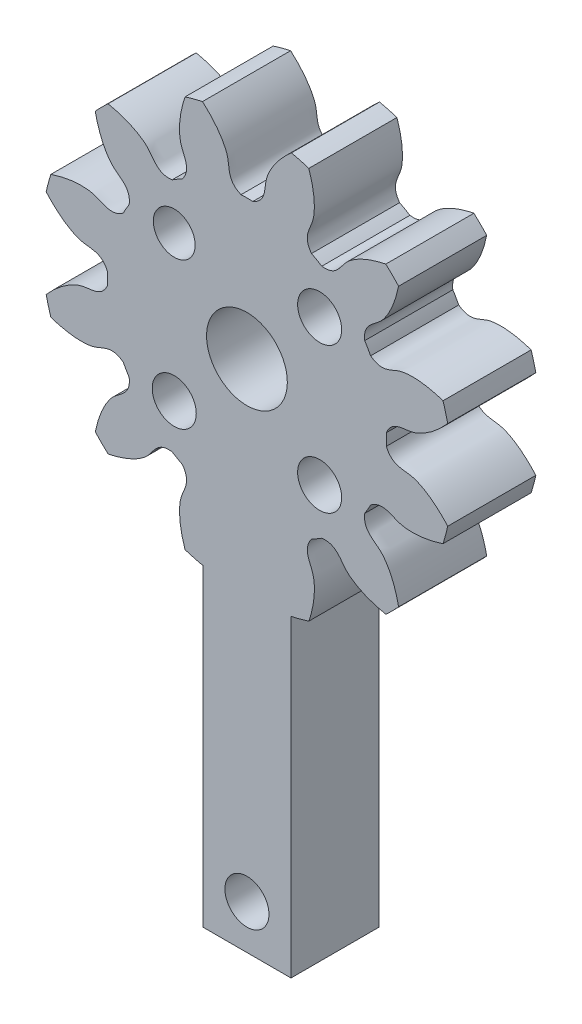
SolidWorks part; units mm, degrees
ref_plane "前视基准面" through (0, 0, 0) normal (0, 0, 1) x (1, 0, 0)
ref_plane "上视基准面" through (0, 0, 0) normal (0, 1, 0) x (1, 0, 0)
ref_plane "右视基准面" through (0, 0, 0) normal (1, 0, 0) x (0, 0, -1)
sketch "草图1" plane through (0, 0, 0) normal (0, 0, 1) x (1, 0, 0)
  circle A0 centre (0, 0) radius 14
extrude "凸台-拉伸1" add sketch "草图1" along normal blind 30
ref_axis "基准轴1" through (0, 0, -1.5) along (0, 0, 1)
sketch "草图2" plane through (0, 0, 0) normal (0, 0, 1) x (1, 0, 0)
  line L0 (0, 0) -> (0, 14) construction
  circle A0 centre (0, 0) radius 14 construction
  arc A1 (0.4017, 9.4915) -> (-0.4017, 9.4915) centre (0, 0) ccw
  arc A2 (6.9952, 15.7899) -> (-6.9952, 15.7899) centre (0, 0) ccw
  spline S0 degree 3 poles (0.4017, 9.4915) (1.3616, 9.8986) (1.1487, 10.6896) (1.3523, 11.379) (1.3652, 11.4198) (1.3805, 11.4647) (1.3981, 11.5135) (1.4183, 11.5661) (1.4413, 11.6225) (1.4671, 11.6826) (1.4961, 11.7462) (1.5282, 11.8133) (1.5637, 11.8838) (1.6028, 11.9576) (1.6455, 12.0345) (1.6919, 12.1144) (1.7423, 12.1973) (1.7968, 12.2829) (1.8555, 12.3712) (1.9185, 12.462) (1.9859, 12.5552) (2.0579, 12.6506) (2.1346, 12.7481) (2.2161, 12.8475) (2.3025, 12.9487) (2.3939, 13.0516) (2.4904, 13.1559) (2.5921, 13.2615) (2.6991, 13.3682) (2.8114, 13.4759) (2.9292, 13.5844) (3.0525, 13.6935) (3.1814, 13.803) (3.316, 13.9128) (3.4563, 14.0226) (3.6023, 14.1323) (3.7542, 14.2418) (3.912, 14.3507) (4.0756, 14.4589) (4.2452, 14.5663) (4.4208, 14.6726) (4.6024, 14.7776) (4.79, 14.8811) (4.9836, 14.983) (5.1832, 15.083) (5.3889, 15.1809) (5.6006, 15.2765) (5.8183, 15.3697) (6.042, 15.4602) (6.2717, 15.5478) (6.5888, 15.6615) (6.8312, 15.7402) (6.9952, 15.7899) knots 0 0 0 0 0.218015 0.222044 0.226546 0.231522 0.236972 0.242897 0.249295 0.256167 0.263513 0.271332 0.279626 0.288394 0.297636 0.307351 0.317541 0.328204 0.339341 0.350953 0.363038 0.375597 0.38863 0.402137 0.416118 0.430573 0.445502 0.460904 0.476781 0.493132 0.509956 0.527255 0.545027 0.563273 0.581994 0.601188 0.620856 0.640998 0.661614 0.682704 0.704268 0.726305 0.748817 0.771803 0.795262 0.819196 0.843603 0.868484 0.89384 0.919669 0.945972 1 1 1 1
  spline S1 degree 3 poles (-0.4017, 9.4915) (-1.3616, 9.8986) (-1.1487, 10.6896) (-1.3523, 11.379) (-1.3652, 11.4198) (-1.3805, 11.4647) (-1.3981, 11.5135) (-1.4183, 11.5661) (-1.4413, 11.6225) (-1.4671, 11.6826) (-1.4961, 11.7462) (-1.5282, 11.8133) (-1.5637, 11.8838) (-1.6028, 11.9576) (-1.6455, 12.0345) (-1.6919, 12.1144) (-1.7423, 12.1973) (-1.7968, 12.2829) (-1.8555, 12.3712) (-1.9185, 12.462) (-1.9859, 12.5552) (-2.0579, 12.6506) (-2.1346, 12.7481) (-2.2161, 12.8475) (-2.3025, 12.9487) (-2.3939, 13.0516) (-2.4904, 13.1559) (-2.5921, 13.2615) (-2.6991, 13.3682) (-2.8114, 13.4759) (-2.9292, 13.5844) (-3.0525, 13.6935) (-3.1814, 13.803) (-3.316, 13.9128) (-3.4563, 14.0226) (-3.6023, 14.1323) (-3.7542, 14.2418) (-3.912, 14.3507) (-4.0756, 14.4589) (-4.2452, 14.5663) (-4.4208, 14.6726) (-4.6024, 14.7776) (-4.79, 14.8811) (-4.9836, 14.983) (-5.1832, 15.083) (-5.3889, 15.1809) (-5.6006, 15.2765) (-5.8183, 15.3697) (-6.042, 15.4602) (-6.2717, 15.5478) (-6.5888, 15.6615) (-6.8312, 15.7402) (-6.9952, 15.7899) knots 0 0 0 0 0.218015 0.222044 0.226546 0.231522 0.236972 0.242897 0.249295 0.256167 0.263513 0.271332 0.279626 0.288394 0.297636 0.307351 0.317541 0.328204 0.339341 0.350953 0.363038 0.375597 0.38863 0.402137 0.416118 0.430573 0.445502 0.460904 0.476781 0.493132 0.509956 0.527255 0.545027 0.563273 0.581994 0.601188 0.620856 0.640998 0.661614 0.682704 0.704268 0.726305 0.748817 0.771803 0.795262 0.819196 0.843603 0.868484 0.89384 0.919669 0.945972 1 1 1 1
extrude "切除-拉伸1" cut sketch "草图2" along normal through all
pattern_circular "阵列(圆周)1" count 12 every 30 about axis through (0, 0, -1.5) along (0, 0, 1) of "切除-拉伸1"
sketch "草图3" plane through (0, 0, 0) normal (0, 0, 1) x (1, 0, 0)
  circle A0 centre (0, 0) radius 12 construction
  dimension "Dn" = 24
sketch "草图4" plane through (0, 0, 30) normal (0, 0, 1) x (1, 0, 0)
  line L0 (-4.75, 8.2272) -> (4.75, 8.2272) construction
  line L1 (4.95, -4.95) -> (-4.95, -4.95) construction
  line L2 (4.95, -4.95) -> (4.95, 4.95) construction
  line L3 (4.95, 4.95) -> (-4.95, 4.95) construction
  line L4 (-4.95, -4.95) -> (-4.95, 4.95) construction
  line L5 (4.95, -4.95) -> (-4.95, 4.95) construction
  line L6 (4.95, 4.95) -> (-4.95, -4.95) construction
  circle A0 centre (4.95, 4.95) radius 1.5
  circle A1 centre (4.95, -4.95) radius 1.5
  circle A2 centre (-4.95, -4.95) radius 1.5
  circle A3 centre (-4.95, 4.95) radius 1.4237
  arc A4 (-4.3979, 8.4207) -> (-5.0936, 8.019) centre (0, 0) ccw construction
  arc A5 (5.0936, 8.019) -> (4.3979, 8.4207) centre (0, 0) ccw construction
  point P0 (0, 0)
  dimension "D3" = 3
  dimension "D1" = 9.9
  dimension "D2" = 9.9
extrude "切除-拉伸2" cut sketch "草图4" against normal blind 10
sketch "草图5" plane through (0, 0, 0) normal (0, 0, -1) x (-1, 0, 0)
  arc A24 (5.0936, 8.019) -> (4.3979, 8.4207) centre (0, 0) ccw
  arc A25 (4.2145, 13.3506) -> (3.0255, 13.6692) centre (0, 0) ccw
  arc A26 (0.4017, 9.4915) -> (-0.4017, 9.4915) centre (0, 0) ccw
  arc A27 (-3.0255, 13.6692) -> (-4.2145, 13.3506) centre (0, 0) ccw
  arc A28 (-4.3979, 8.4207) -> (-5.0936, 8.019) centre (0, 0) ccw
  arc A29 (-9.4547, 10.3251) -> (-10.3251, 9.4547) centre (0, 0) ccw
  arc A30 (-8.019, 5.0936) -> (-8.4207, 4.3979) centre (0, 0) ccw
  arc A31 (-13.3506, 4.2145) -> (-13.6692, 3.0255) centre (0, 0) ccw
  arc A32 (-9.4915, 0.4017) -> (-9.4915, -0.4017) centre (0, 0) ccw
  arc A33 (-13.6692, -3.0255) -> (-13.3506, -4.2145) centre (0, 0) ccw
  arc A34 (-8.4207, -4.3979) -> (-8.019, -5.0936) centre (0, 0) ccw
  arc A35 (-10.3251, -9.4547) -> (-9.4547, -10.3251) centre (0, 0) ccw
  arc A36 (-5.0936, -8.019) -> (-4.3979, -8.4207) centre (0, 0) ccw
  arc A37 (-4.2145, -13.3506) -> (-3.0255, -13.6692) centre (0, 0) ccw
  arc A38 (-0.4017, -9.4915) -> (0.4017, -9.4915) centre (0, 0) ccw
  arc A39 (3.0255, -13.6692) -> (4.2145, -13.3506) centre (0, 0) ccw
  arc A40 (4.3979, -8.4207) -> (5.0936, -8.019) centre (0, 0) ccw
  arc A41 (9.4547, -10.3251) -> (10.3251, -9.4547) centre (0, 0) ccw
  arc A42 (8.019, -5.0936) -> (8.4207, -4.3979) centre (0, 0) ccw
  arc A43 (13.3506, -4.2145) -> (13.6692, -3.0255) centre (0, 0) ccw
  arc A44 (9.4915, -0.4017) -> (9.4915, 0.4017) centre (0, 0) ccw
  arc A45 (13.6692, 3.0255) -> (13.3506, 4.2145) centre (0, 0) ccw
  arc A46 (8.4207, 4.3979) -> (8.019, 5.0936) centre (0, 0) ccw
  arc A47 (10.3251, 9.4547) -> (9.4547, 10.3251) centre (0, 0) ccw
  arc A48 (5.0936, 8.019) -> (4.3979, 8.4207) centre (0, 0) ccw
  arc A49 (4.2145, 13.3506) -> (3.0255, 13.6692) centre (0, 0) ccw
  arc A50 (0.4017, 9.4915) -> (-0.4017, 9.4915) centre (0, 0) ccw
  arc A51 (-3.0255, 13.6692) -> (-4.2145, 13.3506) centre (0, 0) ccw
  arc A52 (-4.3979, 8.4207) -> (-5.0936, 8.019) centre (0, 0) ccw
  arc A53 (-9.4547, 10.3251) -> (-10.3251, 9.4547) centre (0, 0) ccw
  arc A54 (-8.019, 5.0936) -> (-8.4207, 4.3979) centre (0, 0) ccw
  arc A55 (-13.3506, 4.2145) -> (-13.6692, 3.0255) centre (0, 0) ccw
  arc A56 (-9.4915, 0.4017) -> (-9.4915, -0.4017) centre (0, 0) ccw
  arc A57 (-13.6692, -3.0255) -> (-13.3506, -4.2145) centre (0, 0) ccw
  arc A58 (-8.4207, -4.3979) -> (-8.019, -5.0936) centre (0, 0) ccw
  arc A59 (-10.3251, -9.4547) -> (-9.4547, -10.3251) centre (0, 0) ccw
  arc A60 (-5.0936, -8.019) -> (-4.3979, -8.4207) centre (0, 0) ccw
  arc A61 (-4.2145, -13.3506) -> (-3.0255, -13.6692) centre (0, 0) ccw
  arc A62 (-0.4017, -9.4915) -> (0.4017, -9.4915) centre (0, 0) ccw
  arc A63 (3.0255, -13.6692) -> (4.2145, -13.3506) centre (0, 0) ccw
  arc A64 (4.3979, -8.4207) -> (5.0936, -8.019) centre (0, 0) ccw
  arc A65 (9.4547, -10.3251) -> (10.3251, -9.4547) centre (0, 0) ccw
  arc A66 (8.019, -5.0936) -> (8.4207, -4.3979) centre (0, 0) ccw
  arc A67 (13.3506, -4.2145) -> (13.6692, -3.0255) centre (0, 0) ccw
  arc A68 (9.4915, -0.4017) -> (9.4915, 0.4017) centre (0, 0) ccw
  arc A69 (13.6692, 3.0255) -> (13.3506, 4.2145) centre (0, 0) ccw
  arc A70 (8.4207, 4.3979) -> (8.019, 5.0936) centre (0, 0) ccw
  arc A71 (10.3251, 9.4547) -> (9.4547, 10.3251) centre (0, 0) ccw
  spline S24 degree 3 poles (-2368.8794, 1837.9661) (113.0421, -150.6443) (38.3111, 18.3423) (8.7386, 10.1508) (8.4722, 10.0654) (8.2264, 9.9757) (8.0011, 9.883) (7.7961, 9.789) (7.6111, 9.695) (7.4457, 9.6025) (7.2995, 9.5129) (7.172, 9.4276) (7.0778, 9.359) (6.9977, 9.2968) (6.9309, 9.2418) (6.8721, 9.1892) (0.5786, 3.2069) (39.4786, -48.9386) (-2052.1534, 2191.1398) knots -9.086932 -9.086932 -9.086932 -9.086932 0.523219 0.554498 0.583882 0.61137 0.636962 0.660659 0.682459 0.702364 0.720374 0.736487 0.750705 0.757103 0.768478 0.777956 0.781985 3.505334 3.505334 3.505334 3.505334 only from (9.4547, 10.3251) to (5.0936, 8.019)
  spline S25 degree 3 poles (2923.6721, -681.6501) (-62.1215, 9.7202) (2.4879, 2.1045) (4.522, 10.546) (4.5381, 10.6233) (4.556, 10.7301) (4.5718, 10.8554) (4.5842, 10.9992) (4.5917, 11.1614) (4.5929, 11.3419) (4.5862, 11.5403) (4.5702, 11.7563) (4.5437, 11.9893) (4.505, 12.239) (4.453, 12.5046) (4.3862, 12.7855) (-4.0276, 42.7945) (-187.8553, 19.7333) (2778.1998, -1127.4538) knots -2.505338 -2.505338 -2.505338 -2.505338 0.218015 0.222044 0.231522 0.242897 0.256167 0.271332 0.288394 0.307351 0.328204 0.350953 0.375597 0.402137 0.430573 0.460904 0.493132 10.252695 10.252695 10.252695 10.252695 only from (4.3979, 8.4207) to (4.2145, 13.3506)
  spline S26 degree 3 poles (-2970.4928, 407.2856) (173.2195, -73.9407) (24.0073, 35.0405) (2.4924, 13.1601) (2.3045, 12.953) (2.1365, 12.7524) (1.9877, 12.5595) (1.8571, 12.3755) (1.7439, 12.2016) (1.6469, 12.0389) (1.5651, 11.8882) (1.4973, 11.7506) (1.4501, 11.6441) (1.4118, 11.5501) (1.3815, 11.4691) (1.3568, 11.3941) (-1.1024, 3.0665) (58.6587, -22.6428) (-2872.7869, 871.506) knots -9.086932 -9.086932 -9.086932 -9.086932 0.523219 0.554498 0.583882 0.61137 0.636962 0.660659 0.682459 0.702364 0.720374 0.736487 0.750705 0.757103 0.768478 0.777956 0.781985 3.505334 3.505334 3.505334 3.505334 only from (3.0255, 13.6692) to (0.4017, 9.4915)
  spline S27 degree 3 poles (2872.7993, 871.5098) (-58.6589, -22.6429) (1.1024, 3.0665) (-1.3568, 11.3941) (-1.3815, 11.4691) (-1.4194, 11.5705) (-1.4684, 11.687) (-1.5295, 11.8177) (-1.6042, 11.962) (-1.6934, 12.1188) (-1.7984, 12.2873) (-1.9202, 12.4663) (-2.0597, 12.6549) (-2.218, 12.8518) (-2.3959, 13.0558) (-2.5942, 13.2657) (-24.8852, 35.0474) (-172.5541, -76.8381) (2969.7185, 412.6963) knots -2.505338 -2.505338 -2.505338 -2.505338 0.218015 0.222044 0.231522 0.242897 0.256167 0.271332 0.288394 0.307351 0.328204 0.350953 0.375597 0.402137 0.430573 0.460904 0.493132 10.252695 10.252695 10.252695 10.252695 only from (-0.4017, 9.4915) to (-3.0255, 13.6692)
  spline S28 degree 3 poles (-2776.1651, -1132.5267) (186.9828, 22.5752) (3.2707, 42.3496) (-4.4215, 12.6432) (-4.4808, 12.3699) (-4.5259, 12.1121) (-4.5584, 11.8707) (-4.5794, 11.6461) (-4.5906, 11.4389) (-4.5932, 11.2494) (-4.5887, 11.078) (-4.5786, 10.925) (-4.5662, 10.8091) (-4.5524, 10.7085) (-4.5381, 10.6233) (-4.522, 10.546) (-2.4879, 2.1045) (62.1214, 9.7201) (-2923.6594, -681.6471) knots -9.086932 -9.086932 -9.086932 -9.086932 0.523219 0.554498 0.583882 0.61137 0.636962 0.660659 0.682459 0.702364 0.720374 0.736487 0.750705 0.757103 0.768478 0.777956 0.781985 3.505334 3.505334 3.505334 3.505334 only from (-4.2145, 13.3506) to (-4.3979, 8.4207)
  spline S29 degree 3 poles (2052.1623, 2191.1493) (-39.4787, -48.9387) (-0.5786, 3.2069) (-6.8721, 9.1892) (-6.9309, 9.2418) (-7.0145, 9.3106) (-7.1151, 9.387) (-7.2335, 9.4697) (-7.3702, 9.5573) (-7.5259, 9.6485) (-7.7011, 9.7419) (-7.8961, 9.8361) (-8.1112, 9.9296) (-8.3468, 10.021) (-8.6028, 10.1087) (-8.8795, 10.1914) (-39.0749, 17.9093) (-111.0172, -152.8208) (2365.5035, 1842.2647) knots -2.505338 -2.505338 -2.505338 -2.505338 0.218015 0.222044 0.231522 0.242897 0.256167 0.271332 0.288394 0.307351 0.328204 0.350953 0.375597 0.402137 0.430573 0.460904 0.493132 10.252695 10.252695 10.252695 10.252695 only from (-5.0936, 8.019) to (-9.4547, 10.3251)
  spline S30 degree 3 poles (-1837.9661, -2368.8794) (150.6443, 113.0421) (-18.3423, 38.3111) (-10.1508, 8.7386) (-10.0654, 8.4722) (-9.9757, 8.2264) (-9.883, 8.0011) (-9.789, 7.7961) (-9.695, 7.6111) (-9.6025, 7.4457) (-9.5129, 7.2995) (-9.4276, 7.172) (-9.359, 7.0778) (-9.2968, 6.9977) (-9.2418, 6.9309) (-9.1892, 6.8721) (-3.2069, 0.5786) (48.9386, 39.4786) (-2191.1398, -2052.1534) knots -9.086932 -9.086932 -9.086932 -9.086932 0.523219 0.554498 0.583882 0.61137 0.636962 0.660659 0.682459 0.702364 0.720374 0.736487 0.750705 0.757103 0.768478 0.777956 0.781985 3.505334 3.505334 3.505334 3.505334 only from (-10.3251, 9.4547) to (-8.019, 5.0936)
  spline S31 degree 3 poles (681.6501, 2923.6721) (-9.7202, -62.1215) (-2.1045, 2.4879) (-10.546, 4.522) (-10.6233, 4.5381) (-10.7301, 4.556) (-10.8554, 4.5718) (-10.9992, 4.5842) (-11.1614, 4.5917) (-11.3419, 4.5929) (-11.5403, 4.5862) (-11.7563, 4.5702) (-11.9893, 4.5437) (-12.239, 4.505) (-12.5046, 4.453) (-12.7855, 4.3862) (-42.7945, -4.0276) (-19.7333, -187.8553) (1127.4538, 2778.1998) knots -2.505338 -2.505338 -2.505338 -2.505338 0.218015 0.222044 0.231522 0.242897 0.256167 0.271332 0.288394 0.307351 0.328204 0.350953 0.375597 0.402137 0.430573 0.460904 0.493132 10.252695 10.252695 10.252695 10.252695 only from (-8.4207, 4.3979) to (-13.3506, 4.2145)
  spline S32 degree 3 poles (-407.2856, -2970.4928) (73.9407, 173.2195) (-35.0405, 24.0073) (-13.1601, 2.4924) (-12.953, 2.3045) (-12.7524, 2.1365) (-12.5595, 1.9877) (-12.3755, 1.8571) (-12.2016, 1.7439) (-12.0389, 1.6469) (-11.8882, 1.5651) (-11.7506, 1.4973) (-11.6441, 1.4501) (-11.5501, 1.4118) (-11.4691, 1.3815) (-11.3941, 1.3568) (-3.0665, -1.1024) (22.6428, 58.6587) (-871.506, -2872.7869) knots -9.086932 -9.086932 -9.086932 -9.086932 0.523219 0.554498 0.583882 0.61137 0.636962 0.660659 0.682459 0.702364 0.720374 0.736487 0.750705 0.757103 0.768478 0.777956 0.781985 3.505334 3.505334 3.505334 3.505334 only from (-13.6692, 3.0255) to (-9.4915, 0.4017)
  spline S33 degree 3 poles (-871.5098, 2872.7993) (22.6429, -58.6589) (-3.0665, 1.1024) (-11.3941, -1.3568) (-11.4691, -1.3815) (-11.5705, -1.4194) (-11.687, -1.4684) (-11.8177, -1.5295) (-11.962, -1.6042) (-12.1188, -1.6934) (-12.2873, -1.7984) (-12.4663, -1.9202) (-12.6549, -2.0597) (-12.8518, -2.218) (-13.0558, -2.3959) (-13.2657, -2.5942) (-35.0474, -24.8852) (76.8381, -172.5541) (-412.6963, 2969.7185) knots -2.505338 -2.505338 -2.505338 -2.505338 0.218015 0.222044 0.231522 0.242897 0.256167 0.271332 0.288394 0.307351 0.328204 0.350953 0.375597 0.402137 0.430573 0.460904 0.493132 10.252695 10.252695 10.252695 10.252695 only from (-9.4915, -0.4017) to (-13.6692, -3.0255)
  spline S34 degree 3 poles (1132.5267, -2776.1651) (-22.5752, 186.9828) (-42.3496, 3.2707) (-12.6432, -4.4215) (-12.3699, -4.4808) (-12.1121, -4.5259) (-11.8707, -4.5584) (-11.6461, -4.5794) (-11.4389, -4.5906) (-11.2494, -4.5932) (-11.078, -4.5887) (-10.925, -4.5786) (-10.8091, -4.5662) (-10.7085, -4.5524) (-10.6233, -4.5381) (-10.546, -4.522) (-2.1045, -2.4879) (-9.7201, 62.1214) (681.6471, -2923.6594) knots -9.086932 -9.086932 -9.086932 -9.086932 0.523219 0.554498 0.583882 0.61137 0.636962 0.660659 0.682459 0.702364 0.720374 0.736487 0.750705 0.757103 0.768478 0.777956 0.781985 3.505334 3.505334 3.505334 3.505334 only from (-13.3506, -4.2145) to (-8.4207, -4.3979)
  spline S35 degree 3 poles (-2191.1493, 2052.1623) (48.9387, -39.4787) (-3.2069, -0.5786) (-9.1892, -6.8721) (-9.2418, -6.9309) (-9.3106, -7.0145) (-9.387, -7.1151) (-9.4697, -7.2335) (-9.5573, -7.3702) (-9.6485, -7.5259) (-9.7419, -7.7011) (-9.8361, -7.8961) (-9.9296, -8.1112) (-10.021, -8.3468) (-10.1087, -8.6028) (-10.1914, -8.8795) (-17.9093, -39.0749) (152.8208, -111.0172) (-1842.2647, 2365.5035) knots -2.505338 -2.505338 -2.505338 -2.505338 0.218015 0.222044 0.231522 0.242897 0.256167 0.271332 0.288394 0.307351 0.328204 0.350953 0.375597 0.402137 0.430573 0.460904 0.493132 10.252695 10.252695 10.252695 10.252695 only from (-8.019, -5.0936) to (-10.3251, -9.4547)
  spline S36 degree 3 poles (2368.8794, -1837.9661) (-113.0421, 150.6443) (-38.3111, -18.3423) (-8.7386, -10.1508) (-8.4722, -10.0654) (-8.2264, -9.9757) (-8.0011, -9.883) (-7.7961, -9.789) (-7.6111, -9.695) (-7.4457, -9.6025) (-7.2995, -9.5129) (-7.172, -9.4276) (-7.0778, -9.359) (-6.9977, -9.2968) (-6.9309, -9.2418) (-6.8721, -9.1892) (-0.5786, -3.2069) (-39.4786, 48.9386) (2052.1534, -2191.1398) knots -9.086932 -9.086932 -9.086932 -9.086932 0.523219 0.554498 0.583882 0.61137 0.636962 0.660659 0.682459 0.702364 0.720374 0.736487 0.750705 0.757103 0.768478 0.777956 0.781985 3.505334 3.505334 3.505334 3.505334 only from (-9.4547, -10.3251) to (-5.0936, -8.019)
  spline S37 degree 3 poles (-2923.6721, 681.6501) (62.1215, -9.7202) (-2.4879, -2.1045) (-4.522, -10.546) (-4.5381, -10.6233) (-4.556, -10.7301) (-4.5718, -10.8554) (-4.5842, -10.9992) (-4.5917, -11.1614) (-4.5929, -11.3419) (-4.5862, -11.5403) (-4.5702, -11.7563) (-4.5437, -11.9893) (-4.505, -12.239) (-4.453, -12.5046) (-4.3862, -12.7855) (4.0276, -42.7945) (187.8553, -19.7333) (-2778.1998, 1127.4538) knots -2.505338 -2.505338 -2.505338 -2.505338 0.218015 0.222044 0.231522 0.242897 0.256167 0.271332 0.288394 0.307351 0.328204 0.350953 0.375597 0.402137 0.430573 0.460904 0.493132 10.252695 10.252695 10.252695 10.252695 only from (-4.3979, -8.4207) to (-4.2145, -13.3506)
  spline S38 degree 3 poles (2970.4928, -407.2856) (-173.2195, 73.9407) (-24.0073, -35.0405) (-2.4924, -13.1601) (-2.3045, -12.953) (-2.1365, -12.7524) (-1.9877, -12.5595) (-1.8571, -12.3755) (-1.7439, -12.2016) (-1.6469, -12.0389) (-1.5651, -11.8882) (-1.4973, -11.7506) (-1.4501, -11.6441) (-1.4118, -11.5501) (-1.3815, -11.4691) (-1.3568, -11.3941) (1.1024, -3.0665) (-58.6587, 22.6428) (2872.7869, -871.506) knots -9.086932 -9.086932 -9.086932 -9.086932 0.523219 0.554498 0.583882 0.61137 0.636962 0.660659 0.682459 0.702364 0.720374 0.736487 0.750705 0.757103 0.768478 0.777956 0.781985 3.505334 3.505334 3.505334 3.505334 only from (-3.0255, -13.6692) to (-0.4017, -9.4915)
  spline S39 degree 3 poles (-2872.7993, -871.5098) (58.6589, 22.6429) (-1.1024, -3.0665) (1.3568, -11.3941) (1.3815, -11.4691) (1.4194, -11.5705) (1.4684, -11.687) (1.5295, -11.8177) (1.6042, -11.962) (1.6934, -12.1188) (1.7984, -12.2873) (1.9202, -12.4663) (2.0597, -12.6549) (2.218, -12.8518) (2.3959, -13.0558) (2.5942, -13.2657) (24.8852, -35.0474) (172.5541, 76.8381) (-2969.7185, -412.6963) knots -2.505338 -2.505338 -2.505338 -2.505338 0.218015 0.222044 0.231522 0.242897 0.256167 0.271332 0.288394 0.307351 0.328204 0.350953 0.375597 0.402137 0.430573 0.460904 0.493132 10.252695 10.252695 10.252695 10.252695 only from (0.4017, -9.4915) to (3.0255, -13.6692)
  spline S40 degree 3 poles (2776.1651, 1132.5267) (-186.9828, -22.5752) (-3.2707, -42.3496) (4.4215, -12.6432) (4.4808, -12.3699) (4.5259, -12.1121) (4.5584, -11.8707) (4.5794, -11.6461) (4.5906, -11.4389) (4.5932, -11.2494) (4.5887, -11.078) (4.5786, -10.925) (4.5662, -10.8091) (4.5524, -10.7085) (4.5381, -10.6233) (4.522, -10.546) (2.4879, -2.1045) (-62.1214, -9.7201) (2923.6594, 681.6471) knots -9.086932 -9.086932 -9.086932 -9.086932 0.523219 0.554498 0.583882 0.61137 0.636962 0.660659 0.682459 0.702364 0.720374 0.736487 0.750705 0.757103 0.768478 0.777956 0.781985 3.505334 3.505334 3.505334 3.505334 only from (4.2145, -13.3506) to (4.3979, -8.4207)
  spline S41 degree 3 poles (-2052.1623, -2191.1493) (39.4787, 48.9387) (0.5786, -3.2069) (6.8721, -9.1892) (6.9309, -9.2418) (7.0145, -9.3106) (7.1151, -9.387) (7.2335, -9.4697) (7.3702, -9.5573) (7.5259, -9.6485) (7.7011, -9.7419) (7.8961, -9.8361) (8.1112, -9.9296) (8.3468, -10.021) (8.6028, -10.1087) (8.8795, -10.1914) (39.0749, -17.9093) (111.0172, 152.8208) (-2365.5035, -1842.2647) knots -2.505338 -2.505338 -2.505338 -2.505338 0.218015 0.222044 0.231522 0.242897 0.256167 0.271332 0.288394 0.307351 0.328204 0.350953 0.375597 0.402137 0.430573 0.460904 0.493132 10.252695 10.252695 10.252695 10.252695 only from (5.0936, -8.019) to (9.4547, -10.3251)
  spline S42 degree 3 poles (1837.9661, 2368.8794) (-150.6443, -113.0421) (18.3423, -38.3111) (10.1508, -8.7386) (10.0654, -8.4722) (9.9757, -8.2264) (9.883, -8.0011) (9.789, -7.7961) (9.695, -7.6111) (9.6025, -7.4457) (9.5129, -7.2995) (9.4276, -7.172) (9.359, -7.0778) (9.2968, -6.9977) (9.2418, -6.9309) (9.1892, -6.8721) (3.2069, -0.5786) (-48.9386, -39.4786) (2191.1398, 2052.1534) knots -9.086932 -9.086932 -9.086932 -9.086932 0.523219 0.554498 0.583882 0.61137 0.636962 0.660659 0.682459 0.702364 0.720374 0.736487 0.750705 0.757103 0.768478 0.777956 0.781985 3.505334 3.505334 3.505334 3.505334 only from (10.3251, -9.4547) to (8.019, -5.0936)
  spline S43 degree 3 poles (-681.6501, -2923.6721) (9.7202, 62.1215) (2.1045, -2.4879) (10.546, -4.522) (10.6233, -4.5381) (10.7301, -4.556) (10.8554, -4.5718) (10.9992, -4.5842) (11.1614, -4.5917) (11.3419, -4.5929) (11.5403, -4.5862) (11.7563, -4.5702) (11.9893, -4.5437) (12.239, -4.505) (12.5046, -4.453) (12.7855, -4.3862) (42.7945, 4.0276) (19.7333, 187.8553) (-1127.4538, -2778.1998) knots -2.505338 -2.505338 -2.505338 -2.505338 0.218015 0.222044 0.231522 0.242897 0.256167 0.271332 0.288394 0.307351 0.328204 0.350953 0.375597 0.402137 0.430573 0.460904 0.493132 10.252695 10.252695 10.252695 10.252695 only from (8.4207, -4.3979) to (13.3506, -4.2145)
  spline S44 degree 3 poles (407.2856, 2970.4928) (-73.9407, -173.2195) (35.0405, -24.0073) (13.1601, -2.4924) (12.953, -2.3045) (12.7524, -2.1365) (12.5595, -1.9877) (12.3755, -1.8571) (12.2016, -1.7439) (12.0389, -1.6469) (11.8882, -1.5651) (11.7506, -1.4973) (11.6441, -1.4501) (11.5501, -1.4118) (11.4691, -1.3815) (11.3941, -1.3568) (3.0665, 1.1024) (-22.6428, -58.6587) (871.506, 2872.7869) knots -9.086932 -9.086932 -9.086932 -9.086932 0.523219 0.554498 0.583882 0.61137 0.636962 0.660659 0.682459 0.702364 0.720374 0.736487 0.750705 0.757103 0.768478 0.777956 0.781985 3.505334 3.505334 3.505334 3.505334 only from (13.6692, -3.0255) to (9.4915, -0.4017)
  spline S45 degree 3 poles (871.5098, -2872.7993) (-22.6429, 58.6589) (3.0665, -1.1024) (11.3941, 1.3568) (11.4691, 1.3815) (11.5705, 1.4194) (11.687, 1.4684) (11.8177, 1.5295) (11.962, 1.6042) (12.1188, 1.6934) (12.2873, 1.7984) (12.4663, 1.9202) (12.6549, 2.0597) (12.8518, 2.218) (13.0558, 2.3959) (13.2657, 2.5942) (35.0474, 24.8852) (-76.8381, 172.5541) (412.6963, -2969.7185) knots -2.505338 -2.505338 -2.505338 -2.505338 0.218015 0.222044 0.231522 0.242897 0.256167 0.271332 0.288394 0.307351 0.328204 0.350953 0.375597 0.402137 0.430573 0.460904 0.493132 10.252695 10.252695 10.252695 10.252695 only from (9.4915, 0.4017) to (13.6692, 3.0255)
  spline S46 degree 3 poles (-1132.5267, 2776.1651) (22.5752, -186.9828) (42.3496, -3.2707) (12.6432, 4.4215) (12.3699, 4.4808) (12.1121, 4.5259) (11.8707, 4.5584) (11.6461, 4.5794) (11.4389, 4.5906) (11.2494, 4.5932) (11.078, 4.5887) (10.925, 4.5786) (10.8091, 4.5662) (10.7085, 4.5524) (10.6233, 4.5381) (10.546, 4.522) (2.1045, 2.4879) (9.7201, -62.1214) (-681.6471, 2923.6594) knots -9.086932 -9.086932 -9.086932 -9.086932 0.523219 0.554498 0.583882 0.61137 0.636962 0.660659 0.682459 0.702364 0.720374 0.736487 0.750705 0.757103 0.768478 0.777956 0.781985 3.505334 3.505334 3.505334 3.505334 only from (13.3506, 4.2145) to (8.4207, 4.3979)
  spline S47 degree 3 poles (2191.1493, -2052.1623) (-48.9387, 39.4787) (3.2069, 0.5786) (9.1892, 6.8721) (9.2418, 6.9309) (9.3106, 7.0145) (9.387, 7.1151) (9.4697, 7.2335) (9.5573, 7.3702) (9.6485, 7.5259) (9.7419, 7.7011) (9.8361, 7.8961) (9.9296, 8.1112) (10.021, 8.3468) (10.1087, 8.6028) (10.1914, 8.8795) (17.9093, 39.0749) (-152.8208, 111.0172) (1842.2647, -2365.5035) knots -2.505338 -2.505338 -2.505338 -2.505338 0.218015 0.222044 0.231522 0.242897 0.256167 0.271332 0.288394 0.307351 0.328204 0.350953 0.375597 0.402137 0.430573 0.460904 0.493132 10.252695 10.252695 10.252695 10.252695 only from (8.019, 5.0936) to (10.3251, 9.4547)
  spline S48 degree 3 poles (9.4547, 10.3251) (9.309, 10.2963) (9.0672, 10.2418) (8.7386, 10.1508) (8.4722, 10.0654) (8.2264, 9.9757) (8.0011, 9.883) (7.7961, 9.789) (7.6111, 9.695) (7.4457, 9.6025) (7.2995, 9.5129) (7.172, 9.4276) (7.0778, 9.359) (6.9977, 9.2968) (6.9309, 9.2418) (6.8721, 9.1892) (6.3397, 8.6831) (6.1285, 7.8917) (5.0936, 8.019) knots 0.476404 0.476404 0.476404 0.476404 0.523219 0.554498 0.583882 0.61137 0.636962 0.660659 0.682459 0.702364 0.720374 0.736487 0.750705 0.757103 0.768478 0.777956 0.781985 1 1 1 1
  spline S49 degree 3 poles (4.3979, 8.4207) (3.7701, 9.2532) (4.35, 9.8319) (4.522, 10.546) (4.5381, 10.6233) (4.556, 10.7301) (4.5718, 10.8554) (4.5842, 10.9992) (4.5917, 11.1614) (4.5929, 11.3419) (4.5862, 11.5403) (4.5702, 11.7563) (4.5437, 11.9893) (4.505, 12.239) (4.453, 12.5046) (4.3862, 12.7855) (4.3065, 13.0698) (4.2457, 13.2591) (4.2145, 13.3506) knots 0 0 0 0 0.218015 0.222044 0.231522 0.242897 0.256167 0.271332 0.288394 0.307351 0.328204 0.350953 0.375597 0.402137 0.430573 0.460904 0.493132 0.523596 0.523596 0.523596 0.523596
  spline S50 degree 3 poles (3.0255, 13.6692) (2.9137, 13.5714) (2.7316, 13.4033) (2.4924, 13.1601) (2.3045, 12.953) (2.1365, 12.7524) (1.9877, 12.5595) (1.8571, 12.3755) (1.7439, 12.2016) (1.6469, 12.0389) (1.5651, 11.8882) (1.4973, 11.7506) (1.4501, 11.6441) (1.4118, 11.5501) (1.3815, 11.4691) (1.3568, 11.3941) (1.1487, 10.6896) (1.3616, 9.8986) (0.4017, 9.4915) knots 0.476404 0.476404 0.476404 0.476404 0.523219 0.554498 0.583882 0.61137 0.636962 0.660659 0.682459 0.702364 0.720374 0.736487 0.750705 0.757103 0.768478 0.777956 0.781985 1 1 1 1
  spline S51 degree 3 poles (-0.4017, 9.4915) (-1.3616, 9.8986) (-1.1487, 10.6896) (-1.3568, 11.3941) (-1.3815, 11.4691) (-1.4194, 11.5705) (-1.4684, 11.687) (-1.5295, 11.8177) (-1.6042, 11.962) (-1.6934, 12.1188) (-1.7984, 12.2873) (-1.9202, 12.4663) (-2.0597, 12.6549) (-2.218, 12.8518) (-2.3959, 13.0558) (-2.5942, 13.2657) (-2.8053, 13.472) (-2.9527, 13.6056) (-3.0255, 13.6692) knots 0 0 0 0 0.218015 0.222044 0.231522 0.242897 0.256167 0.271332 0.288394 0.307351 0.328204 0.350953 0.375597 0.402137 0.430573 0.460904 0.493132 0.523596 0.523596 0.523596 0.523596
  spline S52 degree 3 poles (-4.2145, 13.3506) (-4.2624, 13.21) (-4.3361, 12.9734) (-4.4215, 12.6432) (-4.4808, 12.3699) (-4.5259, 12.1121) (-4.5584, 11.8707) (-4.5794, 11.6461) (-4.5906, 11.4389) (-4.5932, 11.2494) (-4.5887, 11.078) (-4.5786, 10.925) (-4.5662, 10.8091) (-4.5524, 10.7085) (-4.5381, 10.6233) (-4.522, 10.546) (-4.35, 9.8319) (-3.7701, 9.2532) (-4.3979, 8.4207) knots 0.476404 0.476404 0.476404 0.476404 0.523219 0.554498 0.583882 0.61137 0.636962 0.660659 0.682459 0.702364 0.720374 0.736487 0.750705 0.757103 0.768478 0.777956 0.781985 1 1 1 1
  spline S53 degree 3 poles (-5.0936, 8.019) (-6.1285, 7.8917) (-6.3397, 8.6831) (-6.8721, 9.1892) (-6.9309, 9.2418) (-7.0145, 9.3106) (-7.1151, 9.387) (-7.2335, 9.4697) (-7.3702, 9.5573) (-7.5259, 9.6485) (-7.7011, 9.7419) (-7.8961, 9.8361) (-8.1112, 9.9296) (-8.3468, 10.021) (-8.6028, 10.1087) (-8.8795, 10.1914) (-9.1655, 10.2645) (-9.3599, 10.3064) (-9.4547, 10.3251) knots 0 0 0 0 0.218015 0.222044 0.231522 0.242897 0.256167 0.271332 0.288394 0.307351 0.328204 0.350953 0.375597 0.402137 0.430573 0.460904 0.493132 0.523596 0.523596 0.523596 0.523596
  spline S54 degree 3 poles (-10.3251, 9.4547) (-10.2963, 9.309) (-10.2418, 9.0672) (-10.1508, 8.7386) (-10.0654, 8.4722) (-9.9757, 8.2264) (-9.883, 8.0011) (-9.789, 7.7961) (-9.695, 7.6111) (-9.6025, 7.4457) (-9.5129, 7.2995) (-9.4276, 7.172) (-9.359, 7.0778) (-9.2968, 6.9977) (-9.2418, 6.9309) (-9.1892, 6.8721) (-8.6831, 6.3397) (-7.8917, 6.1285) (-8.019, 5.0936) knots 0.476404 0.476404 0.476404 0.476404 0.523219 0.554498 0.583882 0.61137 0.636962 0.660659 0.682459 0.702364 0.720374 0.736487 0.750705 0.757103 0.768478 0.777956 0.781985 1 1 1 1
  spline S55 degree 3 poles (-8.4207, 4.3979) (-9.2532, 3.7701) (-9.8319, 4.35) (-10.546, 4.522) (-10.6233, 4.5381) (-10.7301, 4.556) (-10.8554, 4.5718) (-10.9992, 4.5842) (-11.1614, 4.5917) (-11.3419, 4.5929) (-11.5403, 4.5862) (-11.7563, 4.5702) (-11.9893, 4.5437) (-12.239, 4.505) (-12.5046, 4.453) (-12.7855, 4.3862) (-13.0698, 4.3065) (-13.2591, 4.2457) (-13.3506, 4.2145) knots 0 0 0 0 0.218015 0.222044 0.231522 0.242897 0.256167 0.271332 0.288394 0.307351 0.328204 0.350953 0.375597 0.402137 0.430573 0.460904 0.493132 0.523596 0.523596 0.523596 0.523596
  spline S56 degree 3 poles (-13.6692, 3.0255) (-13.5714, 2.9137) (-13.4033, 2.7316) (-13.1601, 2.4924) (-12.953, 2.3045) (-12.7524, 2.1365) (-12.5595, 1.9877) (-12.3755, 1.8571) (-12.2016, 1.7439) (-12.0389, 1.6469) (-11.8882, 1.5651) (-11.7506, 1.4973) (-11.6441, 1.4501) (-11.5501, 1.4118) (-11.4691, 1.3815) (-11.3941, 1.3568) (-10.6896, 1.1487) (-9.8986, 1.3616) (-9.4915, 0.4017) knots 0.476404 0.476404 0.476404 0.476404 0.523219 0.554498 0.583882 0.61137 0.636962 0.660659 0.682459 0.702364 0.720374 0.736487 0.750705 0.757103 0.768478 0.777956 0.781985 1 1 1 1
  spline S57 degree 3 poles (-9.4915, -0.4017) (-9.8986, -1.3616) (-10.6896, -1.1487) (-11.3941, -1.3568) (-11.4691, -1.3815) (-11.5705, -1.4194) (-11.687, -1.4684) (-11.8177, -1.5295) (-11.962, -1.6042) (-12.1188, -1.6934) (-12.2873, -1.7984) (-12.4663, -1.9202) (-12.6549, -2.0597) (-12.8518, -2.218) (-13.0558, -2.3959) (-13.2657, -2.5942) (-13.472, -2.8053) (-13.6056, -2.9527) (-13.6692, -3.0255) knots 0 0 0 0 0.218015 0.222044 0.231522 0.242897 0.256167 0.271332 0.288394 0.307351 0.328204 0.350953 0.375597 0.402137 0.430573 0.460904 0.493132 0.523596 0.523596 0.523596 0.523596
  spline S58 degree 3 poles (-13.3506, -4.2145) (-13.21, -4.2624) (-12.9734, -4.3361) (-12.6432, -4.4215) (-12.3699, -4.4808) (-12.1121, -4.5259) (-11.8707, -4.5584) (-11.6461, -4.5794) (-11.4389, -4.5906) (-11.2494, -4.5932) (-11.078, -4.5887) (-10.925, -4.5786) (-10.8091, -4.5662) (-10.7085, -4.5524) (-10.6233, -4.5381) (-10.546, -4.522) (-9.8319, -4.35) (-9.2532, -3.7701) (-8.4207, -4.3979) knots 0.476404 0.476404 0.476404 0.476404 0.523219 0.554498 0.583882 0.61137 0.636962 0.660659 0.682459 0.702364 0.720374 0.736487 0.750705 0.757103 0.768478 0.777956 0.781985 1 1 1 1
  spline S59 degree 3 poles (-8.019, -5.0936) (-7.8917, -6.1285) (-8.6831, -6.3397) (-9.1892, -6.8721) (-9.2418, -6.9309) (-9.3106, -7.0145) (-9.387, -7.1151) (-9.4697, -7.2335) (-9.5573, -7.3702) (-9.6485, -7.5259) (-9.7419, -7.7011) (-9.8361, -7.8961) (-9.9296, -8.1112) (-10.021, -8.3468) (-10.1087, -8.6028) (-10.1914, -8.8795) (-10.2645, -9.1655) (-10.3064, -9.3599) (-10.3251, -9.4547) knots 0 0 0 0 0.218015 0.222044 0.231522 0.242897 0.256167 0.271332 0.288394 0.307351 0.328204 0.350953 0.375597 0.402137 0.430573 0.460904 0.493132 0.523596 0.523596 0.523596 0.523596
  spline S60 degree 3 poles (-9.4547, -10.3251) (-9.309, -10.2963) (-9.0672, -10.2418) (-8.7386, -10.1508) (-8.4722, -10.0654) (-8.2264, -9.9757) (-8.0011, -9.883) (-7.7961, -9.789) (-7.6111, -9.695) (-7.4457, -9.6025) (-7.2995, -9.5129) (-7.172, -9.4276) (-7.0778, -9.359) (-6.9977, -9.2968) (-6.9309, -9.2418) (-6.8721, -9.1892) (-6.3397, -8.6831) (-6.1285, -7.8917) (-5.0936, -8.019) knots 0.476404 0.476404 0.476404 0.476404 0.523219 0.554498 0.583882 0.61137 0.636962 0.660659 0.682459 0.702364 0.720374 0.736487 0.750705 0.757103 0.768478 0.777956 0.781985 1 1 1 1
  spline S61 degree 3 poles (-4.3979, -8.4207) (-3.7701, -9.2532) (-4.35, -9.8319) (-4.522, -10.546) (-4.5381, -10.6233) (-4.556, -10.7301) (-4.5718, -10.8554) (-4.5842, -10.9992) (-4.5917, -11.1614) (-4.5929, -11.3419) (-4.5862, -11.5403) (-4.5702, -11.7563) (-4.5437, -11.9893) (-4.505, -12.239) (-4.453, -12.5046) (-4.3862, -12.7855) (-4.3065, -13.0698) (-4.2457, -13.2591) (-4.2145, -13.3506) knots 0 0 0 0 0.218015 0.222044 0.231522 0.242897 0.256167 0.271332 0.288394 0.307351 0.328204 0.350953 0.375597 0.402137 0.430573 0.460904 0.493132 0.523596 0.523596 0.523596 0.523596
  spline S62 degree 3 poles (-3.0255, -13.6692) (-2.9137, -13.5714) (-2.7316, -13.4033) (-2.4924, -13.1601) (-2.3045, -12.953) (-2.1365, -12.7524) (-1.9877, -12.5595) (-1.8571, -12.3755) (-1.7439, -12.2016) (-1.6469, -12.0389) (-1.5651, -11.8882) (-1.4973, -11.7506) (-1.4501, -11.6441) (-1.4118, -11.5501) (-1.3815, -11.4691) (-1.3568, -11.3941) (-1.1487, -10.6896) (-1.3616, -9.8986) (-0.4017, -9.4915) knots 0.476404 0.476404 0.476404 0.476404 0.523219 0.554498 0.583882 0.61137 0.636962 0.660659 0.682459 0.702364 0.720374 0.736487 0.750705 0.757103 0.768478 0.777956 0.781985 1 1 1 1
  spline S63 degree 3 poles (0.4017, -9.4915) (1.3616, -9.8986) (1.1487, -10.6896) (1.3568, -11.3941) (1.3815, -11.4691) (1.4194, -11.5705) (1.4684, -11.687) (1.5295, -11.8177) (1.6042, -11.962) (1.6934, -12.1188) (1.7984, -12.2873) (1.9202, -12.4663) (2.0597, -12.6549) (2.218, -12.8518) (2.3959, -13.0558) (2.5942, -13.2657) (2.8053, -13.472) (2.9527, -13.6056) (3.0255, -13.6692) knots 0 0 0 0 0.218015 0.222044 0.231522 0.242897 0.256167 0.271332 0.288394 0.307351 0.328204 0.350953 0.375597 0.402137 0.430573 0.460904 0.493132 0.523596 0.523596 0.523596 0.523596
  spline S64 degree 3 poles (4.2145, -13.3506) (4.2624, -13.21) (4.3361, -12.9734) (4.4215, -12.6432) (4.4808, -12.3699) (4.5259, -12.1121) (4.5584, -11.8707) (4.5794, -11.6461) (4.5906, -11.4389) (4.5932, -11.2494) (4.5887, -11.078) (4.5786, -10.925) (4.5662, -10.8091) (4.5524, -10.7085) (4.5381, -10.6233) (4.522, -10.546) (4.35, -9.8319) (3.7701, -9.2532) (4.3979, -8.4207) knots 0.476404 0.476404 0.476404 0.476404 0.523219 0.554498 0.583882 0.61137 0.636962 0.660659 0.682459 0.702364 0.720374 0.736487 0.750705 0.757103 0.768478 0.777956 0.781985 1 1 1 1
  spline S65 degree 3 poles (5.0936, -8.019) (6.1285, -7.8917) (6.3397, -8.6831) (6.8721, -9.1892) (6.9309, -9.2418) (7.0145, -9.3106) (7.1151, -9.387) (7.2335, -9.4697) (7.3702, -9.5573) (7.5259, -9.6485) (7.7011, -9.7419) (7.8961, -9.8361) (8.1112, -9.9296) (8.3468, -10.021) (8.6028, -10.1087) (8.8795, -10.1914) (9.1655, -10.2645) (9.3599, -10.3064) (9.4547, -10.3251) knots 0 0 0 0 0.218015 0.222044 0.231522 0.242897 0.256167 0.271332 0.288394 0.307351 0.328204 0.350953 0.375597 0.402137 0.430573 0.460904 0.493132 0.523596 0.523596 0.523596 0.523596
  spline S66 degree 3 poles (10.3251, -9.4547) (10.2963, -9.309) (10.2418, -9.0672) (10.1508, -8.7386) (10.0654, -8.4722) (9.9757, -8.2264) (9.883, -8.0011) (9.789, -7.7961) (9.695, -7.6111) (9.6025, -7.4457) (9.5129, -7.2995) (9.4276, -7.172) (9.359, -7.0778) (9.2968, -6.9977) (9.2418, -6.9309) (9.1892, -6.8721) (8.6831, -6.3397) (7.8917, -6.1285) (8.019, -5.0936) knots 0.476404 0.476404 0.476404 0.476404 0.523219 0.554498 0.583882 0.61137 0.636962 0.660659 0.682459 0.702364 0.720374 0.736487 0.750705 0.757103 0.768478 0.777956 0.781985 1 1 1 1
  spline S67 degree 3 poles (8.4207, -4.3979) (9.2532, -3.7701) (9.8319, -4.35) (10.546, -4.522) (10.6233, -4.5381) (10.7301, -4.556) (10.8554, -4.5718) (10.9992, -4.5842) (11.1614, -4.5917) (11.3419, -4.5929) (11.5403, -4.5862) (11.7563, -4.5702) (11.9893, -4.5437) (12.239, -4.505) (12.5046, -4.453) (12.7855, -4.3862) (13.0698, -4.3065) (13.2591, -4.2457) (13.3506, -4.2145) knots 0 0 0 0 0.218015 0.222044 0.231522 0.242897 0.256167 0.271332 0.288394 0.307351 0.328204 0.350953 0.375597 0.402137 0.430573 0.460904 0.493132 0.523596 0.523596 0.523596 0.523596
  spline S68 degree 3 poles (13.6692, -3.0255) (13.5714, -2.9137) (13.4033, -2.7316) (13.1601, -2.4924) (12.953, -2.3045) (12.7524, -2.1365) (12.5595, -1.9877) (12.3755, -1.8571) (12.2016, -1.7439) (12.0389, -1.6469) (11.8882, -1.5651) (11.7506, -1.4973) (11.6441, -1.4501) (11.5501, -1.4118) (11.4691, -1.3815) (11.3941, -1.3568) (10.6896, -1.1487) (9.8986, -1.3616) (9.4915, -0.4017) knots 0.476404 0.476404 0.476404 0.476404 0.523219 0.554498 0.583882 0.61137 0.636962 0.660659 0.682459 0.702364 0.720374 0.736487 0.750705 0.757103 0.768478 0.777956 0.781985 1 1 1 1
  spline S69 degree 3 poles (9.4915, 0.4017) (9.8986, 1.3616) (10.6896, 1.1487) (11.3941, 1.3568) (11.4691, 1.3815) (11.5705, 1.4194) (11.687, 1.4684) (11.8177, 1.5295) (11.962, 1.6042) (12.1188, 1.6934) (12.2873, 1.7984) (12.4663, 1.9202) (12.6549, 2.0597) (12.8518, 2.218) (13.0558, 2.3959) (13.2657, 2.5942) (13.472, 2.8053) (13.6056, 2.9527) (13.6692, 3.0255) knots 0 0 0 0 0.218015 0.222044 0.231522 0.242897 0.256167 0.271332 0.288394 0.307351 0.328204 0.350953 0.375597 0.402137 0.430573 0.460904 0.493132 0.523596 0.523596 0.523596 0.523596
  spline S70 degree 3 poles (13.3506, 4.2145) (13.21, 4.2624) (12.9734, 4.3361) (12.6432, 4.4215) (12.3699, 4.4808) (12.1121, 4.5259) (11.8707, 4.5584) (11.6461, 4.5794) (11.4389, 4.5906) (11.2494, 4.5932) (11.078, 4.5887) (10.925, 4.5786) (10.8091, 4.5662) (10.7085, 4.5524) (10.6233, 4.5381) (10.546, 4.522) (9.8319, 4.35) (9.2532, 3.7701) (8.4207, 4.3979) knots 0.476404 0.476404 0.476404 0.476404 0.523219 0.554498 0.583882 0.61137 0.636962 0.660659 0.682459 0.702364 0.720374 0.736487 0.750705 0.757103 0.768478 0.777956 0.781985 1 1 1 1
  spline S71 degree 3 poles (8.019, 5.0936) (7.8917, 6.1285) (8.6831, 6.3397) (9.1892, 6.8721) (9.2418, 6.9309) (9.3106, 7.0145) (9.387, 7.1151) (9.4697, 7.2335) (9.5573, 7.3702) (9.6485, 7.5259) (9.7419, 7.7011) (9.8361, 7.8961) (9.9296, 8.1112) (10.021, 8.3468) (10.1087, 8.6028) (10.1914, 8.8795) (10.2645, 9.1655) (10.3064, 9.3599) (10.3251, 9.4547) knots 0 0 0 0 0.218015 0.222044 0.231522 0.242897 0.256167 0.271332 0.288394 0.307351 0.328204 0.350953 0.375597 0.402137 0.430573 0.460904 0.493132 0.523596 0.523596 0.523596 0.523596
  dimension "D1" = 0
extrude "切除-拉伸3" cut sketch "草图5" against normal blind 24
sketch "草图6" plane through (0, 0, 30) normal (0, 0, 1) x (1, 0, 0)
  circle A0 centre (0, 0) radius 2.75
  dimension "D1" = 5.5
extrude "切除-拉伸4" cut sketch "草图6" against normal blind 24
sketch "草图9" plane through (0, 0, 30) normal (0, 0, 1) x (1, 0, 0)
  line L0 (0, 9.5) -> (0, -9.5) construction
  line L1 (3, -5) -> (-3, -5)
  line L2 (-3, -5) -> (-3, -35)
  line L3 (-3, -35) -> (3, -35)
  line L4 (3, -5) -> (3, -35)
  arc A0 (0.4017, 9.4915) -> (-0.4017, 9.4915) centre (0, 0) ccw construction
  arc A1 (-0.4017, -9.4915) -> (0.4017, -9.4915) centre (0, 0) ccw construction
  point P8 (0, 0)
  point P13 (0, -35)
  point P14 (0, -5)
  dimension "D1" = 3
  dimension "D2" = 30
  dimension "D3" = 5
extrude "凸台-拉伸2" add sketch "草图9" against normal blind 6
sketch "草图10" plane through (0, 0, 30) normal (0, 0, 1) x (1, 0, 0)
  line L0 (0, -35) -> (0, -32) construction
  line L1 (-3, -35) -> (3, -35) construction
  circle A0 centre (0, -32) radius 1.5
  dimension "D1" = 3
  dimension "D2" = 3
extrude "切除-拉伸5" cut sketch "草图10" against normal blind 10
